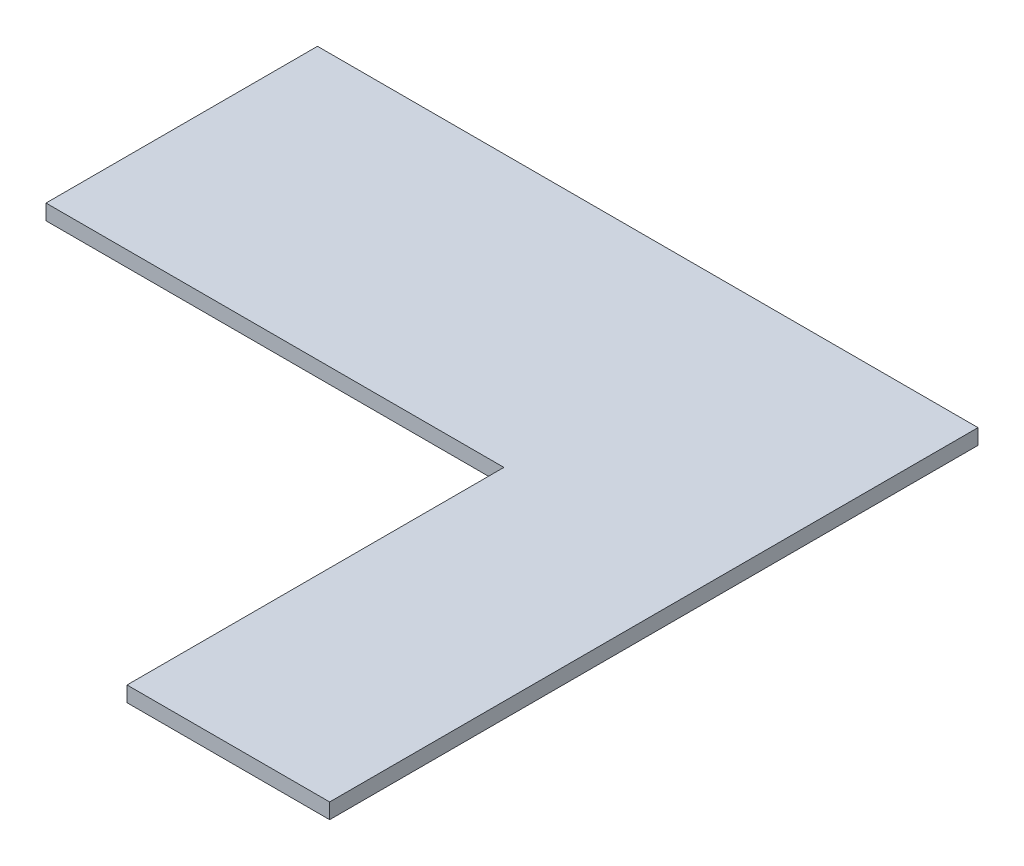
SolidWorks part; units mm, degrees
ref_plane "Спереди" through (0, 0, 0) normal (0, 0, 1) x (1, 0, 0)
ref_plane "Сверху" through (0, 0, 0) normal (0, 1, 0) x (1, 0, 0)
ref_plane "Справа" through (0, 0, 0) normal (1, 0, 0) x (0, 0, -1)
sketch "Эскиз1" plane through (0, 0, 0) normal (0, 1, 0) x (1, 0, 0)
  line L0 (0, 0) -> (0, 670)
  line L1 (0, 670) -> (1630, 670)
  line L2 (1630, 670) -> (1630, -930)
  line L3 (1630, -930) -> (1130, -930)
  line L4 (1130, -930) -> (1130, 0)
  line L5 (1130, 0) -> (0, 0)
extrude "Бобышка-Вытянуть1" add sketch "Эскиз1" along normal blind 38
